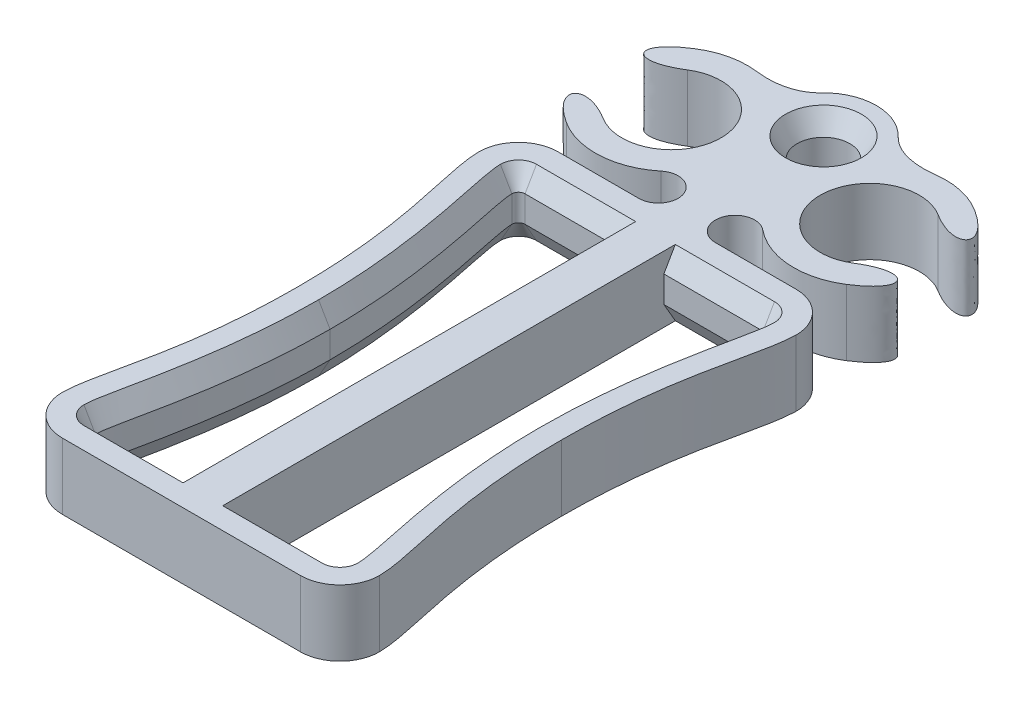
SolidWorks part; units mm, degrees
ref_plane "Спереди" through (0, 0, 0) normal (0, 0, 1) x (1, 0, 0)
ref_plane "Сверху" through (0, 0, 0) normal (0, 1, 0) x (1, 0, 0)
ref_plane "Справа" through (0, 0, 0) normal (1, 0, 0) x (0, 0, -1)
sketch "Ski_clamp_draft" plane through (0, 0, 0) normal (0, 1, 0) x (1, 0, 0)
  line L0 (0, 84.5926) -> (0, -79.9447) construction
  line L1 (-26.7437, 21.5998) -> (-17.1186, 27.7531) construction
  line L2 (-21.9966, 19.9327) -> (-35.1242, 11.7407) construction
  line L5 (-5.7981, 1.3146) -> (-18, 1.3146)
  line L6 (-3, -3.6854) -> (-3, -68.6854)
  line L7 (18, -73.6854) -> (-18, -73.6854)
  line L8 (-18, -3.6854) -> (-3, -3.6854)
  line L9 (-18, -68.6854) -> (-3, -68.6854)
  line L10 (-22.9861, 15.4583) -> (-11.0074, 15.4583) construction
  line L11 (3, -36.1854) -> (31.5715, -36.1854) construction
  line L12 (-20, -47.3104) -> (-20, -26.7143) construction
  line L13 (-3, -36.1854) -> (-31.5715, -36.1854) construction
  line L14 (-15, -48.3778) -> (-15, -24.3498) construction
  line L15 (22.9861, 15.4583) -> (11.0074, 15.4583) construction
  line L16 (18, -68.6854) -> (3, -68.6854)
  line L17 (18, -3.6854) -> (3, -3.6854)
  line L18 (3, -3.6854) -> (3, -68.6854)
  line L19 (5.7981, 1.3146) -> (18, 1.3146)
  arc A0 (-18.9706, 9.0955) -> (-18.9706, 21.8211) centre (-15, 15.4583) ccw
  arc A1 (-21.1943, 5.7691) -> (-7.6883, 6.582) centre (-15, 15.4583) ccw
  arc A4 (-18, -3.6854) -> (-19, -4.6854) centre (-18, -4.6854) ccw
  arc A5 (-18, 1.3146) -> (-24, -4.6854) centre (-18, -4.6854) ccw
  arc A6 (-13.4851, 26.8581) -> (-21.1943, 25.1475) centre (-15, 15.4583) ccw
  arc A7 (-18, -68.6854) -> (-19, -67.6854) centre (-18, -67.6854) cw
  arc A8 (-18, -73.6854) -> (-24, -67.6854) centre (-18, -67.6854) cw
  circle A9 centre (0, 23.4583) radius 4
  circle A11 centre (-15, 15.4583) radius 11.5 construction
  arc A12 (21.1943, 5.7691) -> (7.6883, 6.582) centre (15, 15.4583) cw construction
  arc A13 (18, -73.6854) -> (24, -67.6854) centre (18, -67.6854) ccw
  arc A14 (18, -68.6854) -> (19, -67.6854) centre (18, -67.6854) ccw
  arc A15 (13.4851, 26.8581) -> (21.1943, 25.1475) centre (15, 15.4583) cw
  arc A16 (18, 1.3146) -> (24, -4.6854) centre (18, -4.6854) cw
  arc A17 (18, -3.6854) -> (19, -4.6854) centre (18, -4.6854) cw
  arc A18 (21.1943, 5.7691) -> (7.6883, 6.582) centre (15, 15.4583) cw
  arc A19 (18.9706, 9.0955) -> (18.9706, 21.8211) centre (15, 15.4583) cw
  arc A20 (5.8165, 28.9509) -> (-5.8165, 28.9509) centre (0, 23.4583) ccw
  arc A21 (13.4851, 26.8581) -> (21.1943, 25.1475) centre (15, 15.4583) cw construction
  arc A22 (-5.7981, 1.3146) -> (-7.6883, 6.582) centre (-5.7981, 4.2875) ccw
  arc A23 (5.7981, 1.3146) -> (7.6883, 6.582) centre (5.7981, 4.2875) cw
  circle A24 centre (0, 23.4583) radius 5.5 construction
  spline S0 degree 3 poles (-24, -4.6854) (-23.89, -10.2637) (-20, -18.869) (-20, -36.1854) knots 0 0 0 0 1 1 1 1
  spline S1 degree 3 poles (-19, -4.6854) (-19, -7.7925) (-15, -20.0895) (-15, -36.1854) knots 0 0 0 0 1 1 1 1
  spline S2 degree 3 poles (-21.1943, 25.1475) (-27.21, 21.3017) (-24.603, 18.3063) (-18.9706, 21.8211) knots 0 0 0 0 1 1 1 1
  spline S3 degree 3 poles (-21.1943, 5.7691) (-27.21, 9.6149) (-24.603, 12.6103) (-18.9706, 9.0955) knots 0 0 0 0 1 1 1 1
  spline S4 degree 3 poles (-13.4851, 26.8581) (-10.1274, 26.4119) (-7.3822, 27.2928) (-5.8165, 28.9509) knots 0 0 0 0 1 1 1 1
  spline S5 degree 3 poles (-24, -67.6854) (-23.89, -62.107) (-20, -53.5018) (-20, -36.1854) knots 0 0 0 0 1 1 1 1
  spline S6 degree 3 poles (-19, -67.6854) (-19, -64.5782) (-15, -52.2812) (-15, -36.1854) knots 0 0 0 0 1 1 1 1
  spline S7 degree 3 poles (19, -67.6854) (19, -64.5782) (15, -52.2812) (15, -36.1854) knots 0 0 0 0 1 1 1 1
  spline S8 degree 3 poles (24, -67.6854) (23.89, -62.107) (20, -53.5018) (20, -36.1854) knots 0 0 0 0 1 1 1 1
  spline S9 degree 3 poles (21.1943, 5.7691) (27.21, 9.6149) (24.603, 12.6103) (18.9706, 9.0955) knots 0 0 0 0 1 1 1 1
  spline S10 degree 3 poles (21.1943, 25.1475) (27.21, 21.3017) (24.603, 18.3063) (18.9706, 21.8211) knots 0 0 0 0 1 1 1 1
  spline S11 degree 3 poles (19, -4.6854) (19, -7.7925) (15, -20.0895) (15, -36.1854) knots 0 0 0 0 1 1 1 1
  spline S12 degree 3 poles (24, -4.6854) (23.89, -10.2637) (20, -18.869) (20, -36.1854) knots 0 0 0 0 1 1 1 1
  spline S13 degree 3 poles (13.4851, 26.8581) (10.1274, 26.4119) (7.3822, 27.2928) (5.8165, 28.9509) knots 0 0 0 0 1 1 1 1
  point P5 (-14.1826, 18.6423)
  point P20 (-12.6355, 13.6757)
  point P25 (-12.6184, 15.1283)
  point P42 (-11.7995, 14.8909)
  point P43 (0, 28.1173)
  point P44 (-15, 15.4583)
  point P49 (-3, 5.2915)
  point P82 (0, -73.6854)
  dimension "D2" = 15
  dimension "D3" = 4
  dimension "D8" = 2
  dimension "D6" = 5
  dimension "D7" = 8
  dimension "D12" = 4
  dimension "D13" = 1.5
  dimension "D1" = 65
  dimension "D4" = 5
  dimension "D5" = 5
  dimension "D9" = 6
  dimension "D10" = 12
  dimension "D11" = 3
extrude "Ski_clamp" add sketch "Ski_clamp_draft" along normal blind 10 contours A15 S13 A20 S4 A6 S2 A0 S3 A1 L5 A5 S0 S5 A8 L7 A13 S8 S12 A16 L19 A18 S9 A19 S10 A17 S11 S7 A14 L16 L18 L17 A7 S6 S1 A4 L8 L6 L9 A9 region at (0, 0, 20.4794)
chamfer "ang30" distance 3 angle 30 26 edges at (-10.5, 10, 68.6854) (-10.5, 10, 3.6854) (-18.7071, 10, 3.9783) (-18.7071, 10, 68.3925) (10.5, 10, 68.6854) (18.7071, 10, 68.3925) (18.7071, 10, 3.9783) (10.5, 10, 3.6854) (-18.7071, 0, 68.3925) (-18.7071, 0, 3.9783) (-10.5, 0, 3.6854) (-10.5, 0, 68.6854) (10.5, 0, 68.6854) (10.5, 0, 3.6854) (18.7071, 0, 3.9783) (18.7071, 0, 68.3925) (0, 0, -19.4583) (0, 10, -19.4583) first distance on face at (-10.5, 5, 68.6854) first distance on face at (-10.5, 5, 3.6854) first distance on face at (-18.6036, 5, 4.0818) first distance on face at (-18.6036, 5, 68.2889) first distance on face at (-18, 5, 12.5604) first distance on face at (-18, 5, 59.8104) first distance on face at (10.5, 5, 68.6854) first distance on face at (18.6036, 5, 68.2889) first distance on face at (18, 5, 59.8104) first distance on face at (18, 5, 12.5604) first distance on face at (18.6036, 5, 4.0818) first distance on face at (10.5, 5, 3.6854) first distance on face at (0, 10, -19.4583)
